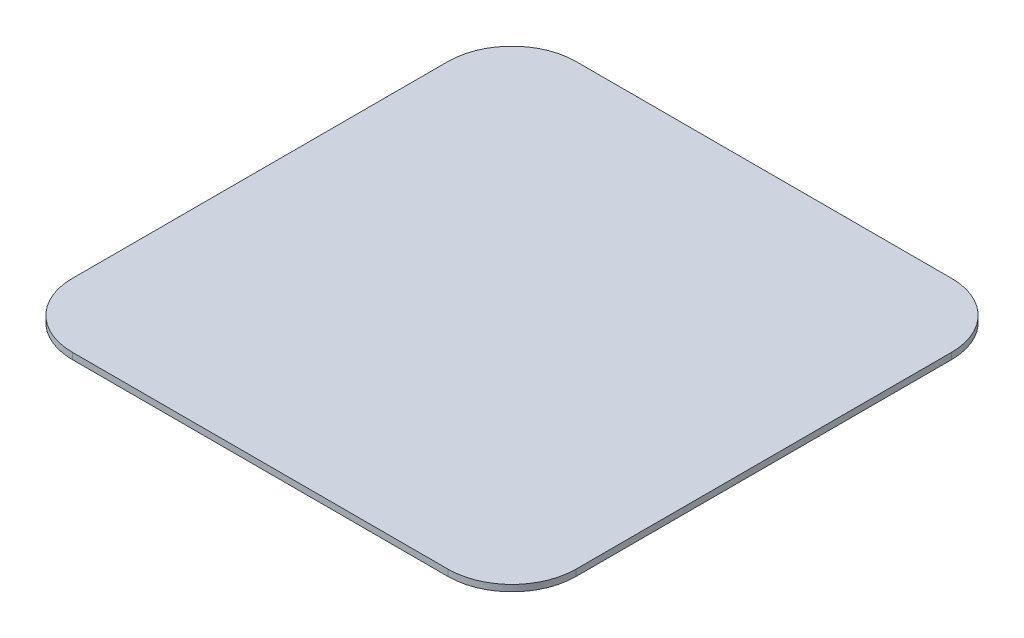
SolidWorks part; units mm, degrees
material "PVC Rigid"
ref_plane "Front Plane" through (0, 0, 0) normal (0, 0, 1) x (1, 0, 0)
ref_plane "Top Plane" through (0, 0, 0) normal (0, 1, 0) x (1, 0, 0)
ref_plane "Right Plane" through (0, 0, 0) normal (1, 0, 0) x (0, 0, -1)
sketch "Sketch1" plane through (0, 0, 0) normal (0, 1, 0) x (1, 0, 0)
  line L1 (0, 0) -> (2000, 0)
  line L2 (0, 0) -> (0, 2000)
  line L3 (0, 2000) -> (2000, 2000)
  line L4 (2000, 0) -> (2000, 2000)
  dimension "D1" = 2000
  dimension "D2" = 2000
extrude "Extrude1" add sketch "Sketch1" along normal blind 25.4
fillet "Fillet1" radius 254 4 edges at (0, 12.7, -2000) (2000, 12.7, -2000) (2000, 12.7, 0) (0, 12.7, 0)
sketch "Sketch2" plane through (0, 0, 0) normal (0, -1, 0) x (1, 0, 0)
  line L0 (0, -1051.6337) -> (2000, -1051.6337)
  line L1 (0, -1746) -> (0, -254) construction
  line L2 (2000, -254) -> (2000, -1746) construction
split line "Split Line1" [suppressed]
sketch "Sketch3" [suppressed] plane through (0, 0, 0) normal (0, -1, 0) x (1, 0, 0)
  line L0 (0, -871.6337) -> (2000, -871.6337)
  line L1 (0, -1051.6337) -> (0, -254) construction
  line L2 (2000, -254) -> (2000, -1051.6337) construction
  line L3 (2000, -1051.6337) -> (0, -1051.6337) construction
  dimension "D1" = 180
split line "Split Line2" [suppressed]
